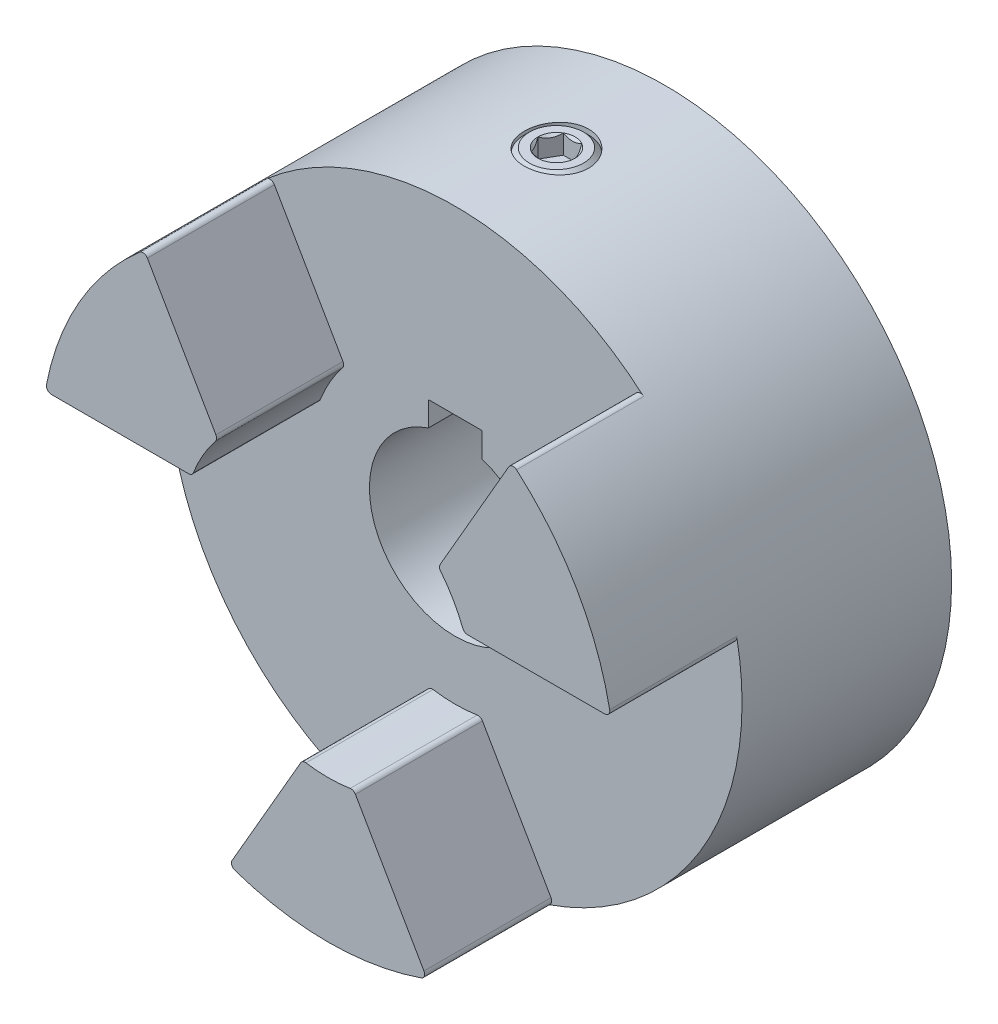
SolidWorks part; units mm, degrees
ref_plane "Front" through (0, 0, 0) normal (0, 0, 1) x (1, 0, 0)
ref_plane "Top" through (0, 0, 0) normal (0, 1, 0) x (1, 0, 0)
ref_plane "Right" through (0, 0, 0) normal (1, 0, 0) x (0, 0, -1)
sketch "Sketch3" plane through (0, 0, 0) normal (1, 0, 0) x (0, 0, -1)
  line L0 (27.3844, 0) -> (-27.3844, 0) construction
  circle A0 centre (0, 0) radius 5.1149 construction
  circle A1 centre (0, 0) radius 8 construction
  circle A2 centre (0, 0) radius 26.7891 construction
  point P7 (0, 5.1149)
  point P8 (0, -5.1149)
  point P9 (0, 8)
  point P10 (0, -8)
  point P11 (0, 26.7891)
  point P12 (0, -26.7891)
  point P13 (6.7469, 0)
  point P14 (-5.1149, 0)
  point P15 (5.1149, 0)
  point P16 (-5.1149, 26.7891)
  point P17 (27.3844, 26.7891)
  point P18 (6.7469, 26.7891)
sketch "Sketch1" plane through (0, 0, 0) normal (0, 0, 1) x (1, 0, 0)
  circle A0 centre (0, 0) radius 26.7891
  circle A1 centre (0, 0) radius 8 construction
extrude "Boss-Extrude1" add sketch "Sketch1" against normal up to vertex (27.3844 mm away) from vertex at -6.7469 starting at point (0, 0, -6.7469)
sketch "Sketch10" [suppressed] plane through (0, 0, -3.5719) normal (0, 0, 1) x (1, 0, 0)
  arc A14 (-1.0963, -4.1108) -> (1.0963, -4.1108) centre (0, 0) ccw
  arc A15 (-3.4409, -7.1529) -> (-1.0963, -4.1108) centre (-9.5758, 0) ccw
  arc A19 (1.0963, -4.1108) -> (3.4409, -7.1529) centre (9.5758, 0) ccw
  circle A32 centre (0, 0) radius 7.9375 construction
  arc A33 (-3.4409, -7.1529) -> (3.4409, -7.1529) centre (0, 0) ccw
  point P0 (0, -4.2545)
  point P1 (0, -7.9375)
  dimension "D1" = 3.683
  dimension "D4" = 9.4234
  dimension "D2" = 6.8819
  dimension "D3" = 2.1926
extrude "Boss-Extrude4" [suppressed] add sketch "Sketch10" along normal up to vertex
fillet "Fillet2" [suppressed] radius 0.381
other "Move Face3" [suppressed] parameters "D1"=90
pattern_circular "CirPattern2" [suppressed] count 2 over 360
sketch "Sketch11" [suppressed] plane through (0, 0, -5.9531) normal (0, 0, 1) x (1, 0, 0)
  arc A0 (-1.5825, -7.8835) -> (1.5738, -7.8835) centre (-0.0044, -0.0397) ccw
  arc A1 (-1.5825, -7.8835) -> (-2.9616, -8.354) centre (-1.8681, -9.3029) ccw
  arc A2 (-2.9616, -8.354) -> (-4.9794, -11.8231) centre (5.1535, -15.3956) ccw
  arc A3 (-4.9794, -11.8231) -> (-4.4308, -12.9555) centre (-4.1442, -12.1175) ccw
  arc A4 (-4.4308, -12.9555) -> (4.4176, -12.96) centre (0, 0) ccw
  arc A5 (4.4176, -12.96) -> (4.9692, -11.8231) centre (4.1308, -12.1185) ccw
  arc A6 (4.9692, -11.8231) -> (2.9523, -8.354) centre (-5.1643, -15.3938) ccw
  arc A7 (2.9523, -8.354) -> (1.5738, -7.8835) centre (1.8592, -9.3021) ccw
  circle A8 centre (0, 0) radius 13.6922 construction
  point P18 (-0.007, -13.6922)
  point P19 (-0.0044, -8.0407)
  dimension "D1" = 1.4478
  dimension "D2" = 8.001
  dimension "D3" = 10.7442
  dimension "D4" = 0.889
  dimension "D9" = 5.6515
  dimension "D5" = 5.072
  dimension "D6" = 3.1563
  dimension "D7" = 5.9139
  dimension "D8" = 9.9486
extrude "Boss-Extrude5" [suppressed] add sketch "Sketch11" along normal up to vertex
other "Move Face1" [suppressed] parameters "D1"=90
pattern_circular "CirPattern3" [suppressed] count 2 over 360
sketch "Sketch12" [suppressed] plane through (0, 0, -6.1516) normal (0, 0, 1) x (1, 0, 0)
  line L0 (-5.1097, -10.267) -> (-8.533, -13.6894)
  line L1 (8.533, -13.6894) -> (5.1097, -10.267)
  arc A0 (-2.3442, -9.4968) -> (2.3442, -9.4968) centre (0, 0) ccw
  arc A1 (-2.3442, -9.4968) -> (-5.1097, -10.267) centre (-3.0443, -12.333) ccw
  arc A2 (-8.533, -13.6894) -> (-8.3299, -15.1215) centre (-7.8934, -14.3292) ccw
  arc A3 (-8.3299, -15.1215) -> (8.3299, -15.1215) centre (0, 0) ccw
  arc A4 (8.3299, -15.1215) -> (8.533, -13.6894) centre (7.8934, -14.3292) ccw
  arc A5 (5.1097, -10.267) -> (2.3442, -9.4968) centre (3.0443, -12.333) ccw
  circle A6 centre (0, 0) radius 17.2641 construction
  point P16 (0, -9.7819)
  point P17 (0, -17.2641)
  dimension "D1" = 7.4822
  dimension "D2" = 10.2193
  dimension "D3" = 4.6884
  dimension "D4" = 17.066
  dimension "D5" = 16.6598
extrude "Boss-Extrude6" [suppressed] add sketch "Sketch12" along normal up to vertex
other "Move Face2" [suppressed] parameters "D1"=90
pattern_circular "CirPattern4" [suppressed] count 2 over 360
sketch "Sketch2" plane through (0, 0, -6.7469) normal (0, 0, 1) x (1, 0, 0)
  line L0 (-9.2385, -25.1456) -> (-2.385, -13.2749)
  line L2 (2.385, -13.2749) -> (9.2385, -25.1456)
  circle A0 centre (0, 0) radius 26.7891 construction
  arc A1 (-9.2385, -25.1456) -> (9.2385, -25.1456) centre (0, 0) ccw
  arc A2 (-2.385, -13.2749) -> (2.385, -13.2749) centre (0, 0) ccw
  circle A3 centre (0, 0) radius 4.572 construction
  dimension "D1" = 60
extrude "Boss-Extrude2" add sketch "Sketch2" along normal up to vertex (21.4313 mm away)
fillet "Fillet1" radius 0.477 4 edges at (2.385, -13.2749, -0.816) (-2.385, -13.2749, -0.816)
pattern_circular "CirPattern1" count 3 over 360 about axis through (0, 0, 0) along (0, 0, 1) of "Boss-Extrude2", "Fillet1"
sketch "Sketch15" plane through (0, 0, 0) normal (0, 0, 1) x (1, 0, 0)
  circle A0 centre (0, 0) radius 8
extrude "Cut-Extrude5" cut sketch "Sketch15" against normal through all and the other way through all
chamfer "Chamfer1" distance 1.0716 angle 56 2 edges at (26.7891, 0, -27.3844) (8, 0, -27.3844)
sketch "Sketch4" plane through (0, 0, 0) normal (0, 0, 1) x (1, 0, 0)
  line L1 (-2.5, 9.8993) -> (2.5, 9.8993)
  line L2 (-2.5, 9.8993) -> (-2.5, 7.5993)
  line L4 (2.5, 9.8993) -> (2.5, 7.5993)
  arc A1 (2.5, 7.5993) -> (-2.5, 7.5993) centre (0, 0) ccw
  circle A2 centre (0, 0) radius 8 construction
  dimension "Keyway Ht" = 2.3
  dimension "Keyway Wd" = 5
extrude "Cut-Extrude1" cut sketch "Sketch4" against normal through all and the other way through all
sketch "Sketch5" plane through (0, 0, 0) normal (0, 1, 0) x (1, 0, 0)
  line L1 (0, -46.4939) -> (0, 46.4939) construction
  circle A0 centre (0, 16.2084) radius 3
extrude "Cut-Extrude2" cut sketch "Sketch5" along normal through all
ref_plane "Plane1" through (0, 26.7891, 0) normal (0, 1, 0) x (-1, 0, 0)
sketch "Sketch6" plane through (0, 26.7891, 0) normal (0, 1, 0) x (-1, 0, 0)
  circle A1 centre (0, -16.2084) radius 3
  circle A2 centre (0, -16.2084) radius 3
  dimension "D1" = 0
extrude "Boss-Extrude3" add sketch "Sketch6" against normal blind 8 separate body
sketch "Sketch8" plane through (0, 26.7891, 0) normal (0, 1, 0) x (1, 0, 0)
  line L1 (0.866, 14.7084) -> (1.7321, 16.2084)
  line L2 (1.7321, 16.2084) -> (0.866, 17.7084)
  line L3 (0.866, 17.7084) -> (-0.866, 17.7084)
  line L4 (-0.866, 17.7084) -> (-1.7321, 16.2084)
  line L5 (-1.7321, 16.2084) -> (-0.866, 14.7084)
  line L6 (-0.866, 14.7084) -> (0.866, 14.7084)
  circle A0 centre (0, 16.2084) radius 1.5 construction
  dimension "D1" = 3
extrude "Cut-Extrude3" cut sketch "Sketch8" against normal blind 1.8
sketch "Sketch9" plane through (0, 26.7891, 0) normal (0, 1, 0) x (1, 0, 0)
  circle A0 centre (0, 16.2084) radius 1.7321
extrude "Cut-Extrude4" cut sketch "Sketch9" against normal through all draft 45
chamfer "Chamfer3" distance 0.48 angle 45 1 edges at (0, 26.7891, -13.2084)
chamfer "Chamfer4" distance 1.02 angle 45 1 edges at (0, 18.7891, -13.2084)
sketch "Sketch16" [suppressed] plane through (0, 0, -61.9125) normal (0, 0, -1) x (-1, 0, 0)
  circle A0 centre (0, 0) radius 50.8
  dimension "D1" = 101.6
extrude "Cut-Extrude6" [suppressed] cut sketch "Sketch16" against normal blind 30.3022 flip side to cut
chamfer "Chamfer5" [suppressed] distance 1.778 angle 56
fillet "Fillet3" [suppressed] radius 1.27
move or copy body "Body-Move/Copy1" [suppressed] bodies to move or copy 115 copy no translate (0, -6.35, 0)
sketch "Sketch17" [suppressed] plane through (0, 0, -67.8656) normal (0, 0, -1) x (-1, 0, 0)
  circle A0 centre (0, 0) radius 53.975
  dimension "D1" = 107.95
extrude "Cut-Extrude7" [suppressed] cut sketch "Sketch17" against normal blind 36.576 flip side to cut
move or copy body "Body-Move/Copy2" [suppressed] bodies to move or copy 115 copy no translate (0, -9.525, 0)
fillet "Fillet4" [suppressed] radius 2.54
fillet "Fillet5" [suppressed] radius 1.27
equation "\"D1@Chamfer1\" = \"OD@Sketch3\" * .02"
equation "\"D1@Fillet1\" = \"D4@Sketch2\" * .1"
equation "\"D1@Sketch8\" = \"Screw Dia@Sketch5\" * .5"
equation "\"D1@Cut-Extrude3\" = \"Screw Dia@Sketch5\" * .3"
equation "\"D1@Chamfer3\" = \"Screw Dia@Sketch5\" * .08"
equation "\"D1@Chamfer4\" = \"Screw Dia@Sketch5\" * .17"
